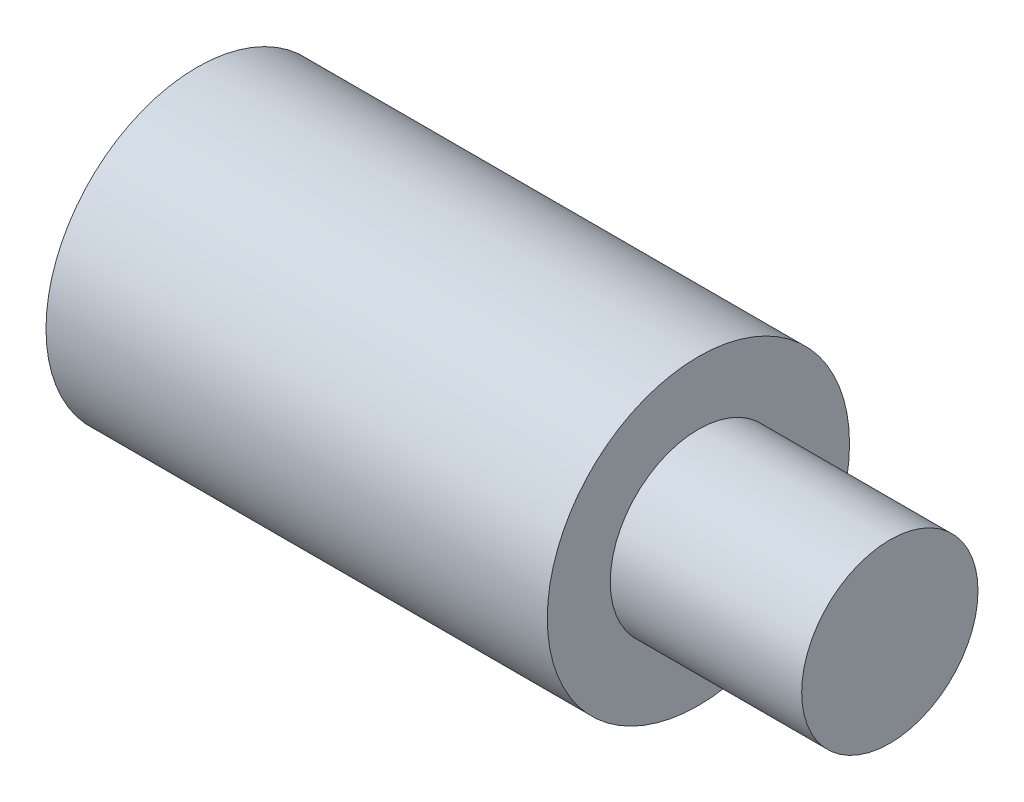
SolidWorks part; units mm, degrees
ref_plane "Front Plane" through (0, 0, 0) normal (0, 0, 1) x (1, 0, 0)
ref_plane "Top Plane" through (0, 0, 0) normal (0, 1, 0) x (1, 0, 0)
ref_plane "Right Plane" through (0, 0, 0) normal (1, 0, 0) x (0, 0, -1)
sketch "Conn_T2_ORB2 Sketch" plane through (0, 0, 0) normal (0, 0, 1) x (1, 0, 0)
  line L0 (-300, 0) -> (300, 0) construction
  line L1 (7.6, 0) -> (7.6, 3.5)
  line L2 (7.6, 3.5) -> (0, 3.5)
  line L3 (0, 3.5) -> (0, 6)
  line L4 (0, 6) -> (-19.9, 6)
  line L5 (-19.9, 6) -> (-19.9, 0)
  line L6 (-19.9, 0) -> (7.6, 0)
revolve "Conn_T2_ORB2" add sketch "Conn_T2_ORB2 Sketch" angle 360 about L0
ref_axis "Engine Axis" through (8.975, 0, 0) along (-1, 0, 0)
sketch "Socket Sketch" plane through (0, 0, 0) normal (0, 0, 1) x (1, 0, 0)
  line L0 (-300, 0) -> (300, 0) construction
  line L1 (-20.9, 0) -> (-20.9, 1.5875)
  line L2 (-20.9, 1.5875) -> (-7.2, 1.5875)
  line L3 (-7.2, 1.5875) -> (-7.2, 0)
  line L4 (-7.2, 0) -> (-20.9, 0)
revolve "Socket" cut sketch "Socket Sketch" angle 360 about L0
